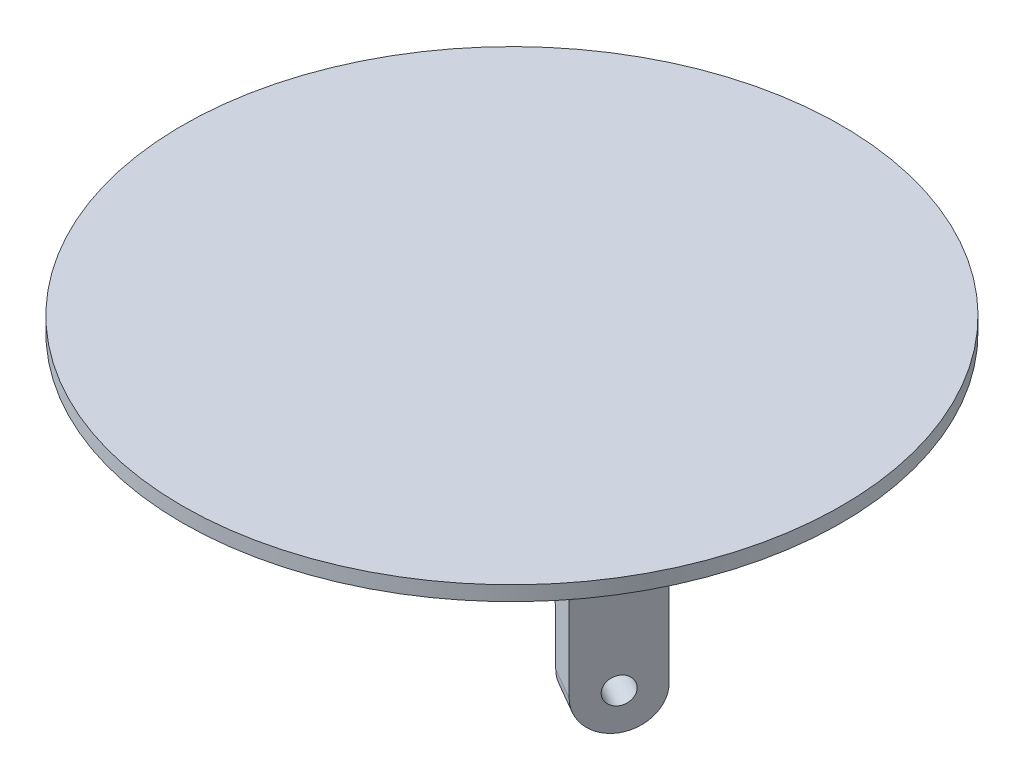
SolidWorks part; units mm, degrees
ref_plane "Front Plane" through (0, 0, 0) normal (0, 0, 1) x (1, 0, 0)
ref_plane "Top Plane" through (0, 0, 0) normal (0, 1, 0) x (1, 0, 0)
ref_plane "Right Plane" through (0, 0, 0) normal (1, 0, 0) x (0, 0, -1)
sketch "Sketch2" plane through (0, 0, 0) normal (0, 1, 0) x (1, 0, 0)
  line L0 (0, 0) -> (-5, 2.8868)
  line L4 (-5, 2.8868) -> (-5, 40)
  line L5 (-5, 40) -> (5, 40)
  line L6 (5, 40) -> (5, 2.8868)
  line L7 (5, 2.8868) -> (0, 0)
  line L8 (0, 0) -> (0, 124.9609) construction
  dimension "D1" = 120
  dimension "D2" = 60
  dimension "D3" = 10
  dimension "D4" = 40
extrude "Boss-Extrude1" add sketch "Sketch2" along normal blind 20
sketch "Sketch3" plane through (5, 0, 0) normal (1, 0, 0) x (0, 0, -1)
  line L0 (40, 20) -> (40, 0) construction
  line L1 (0, 0) -> (35, 0)
  line L2 (0, 0) -> (0, 15)
  line L3 (0, 15) -> (35, 15)
  line L4 (35, 0) -> (35, 15)
  dimension "D1" = 15
  dimension "D3" = 5
extrude "Cut-Extrude1" cut sketch "Sketch3" against normal up to next
fillet "Fillet1" radius 5 2 edges at (-5, 0, -37.5) (5, 0, -37.5)
fillet "Fillet2" radius 3.4 2 edges at (0, 15, -35) (0, 20, -40)
sketch "Sketch4" plane through (0, 0, -40) normal (0, 0, -1) x (-1, 0, 0)
  circle A0 centre (0, 5) radius 1.7
  point P0 (0, 5)
  dimension "D1" = 3.4
hole_wizard "M3 Clearance Hole1" positions "Sketch4" profile "Sketch5" hole size "M3" standard "ANSI Metric" end condition up to next
sketch "Sketch5" plane through (0, 5, -40) normal (1, 0, 0) x (0, 1, 0)
  line L0 (0, 0) -> (0, 5)
  line L1 (0, 5) -> (1.8, 5)
  line L2 (1.8, 5) -> (1.8, 0)
  line L5 (1.8, 0) -> (0, 0)
  line L11 (0, -6.35) -> (0, 107.95) construction
  dimension "Thru Hole Dia." = 3.6
  dimension "Thru Hole Depth" = 5
pattern_circular "CirPattern1" count 3 every 120 about axis through (0, 20, 0) along (0, -1, 0) of "Boss-Extrude1", "Fillet1", "Fillet2", "Cut-Extrude1", "M3 Clearance Hole1"
sketch "Sketch6" plane through (0, 20, 0) normal (0, 1, 0) x (1, 0, 0)
  circle A0 centre (0, 0) radius 45
  dimension "D1" = 90
extrude "Boss-Extrude2" add sketch "Sketch6" along normal blind 2
